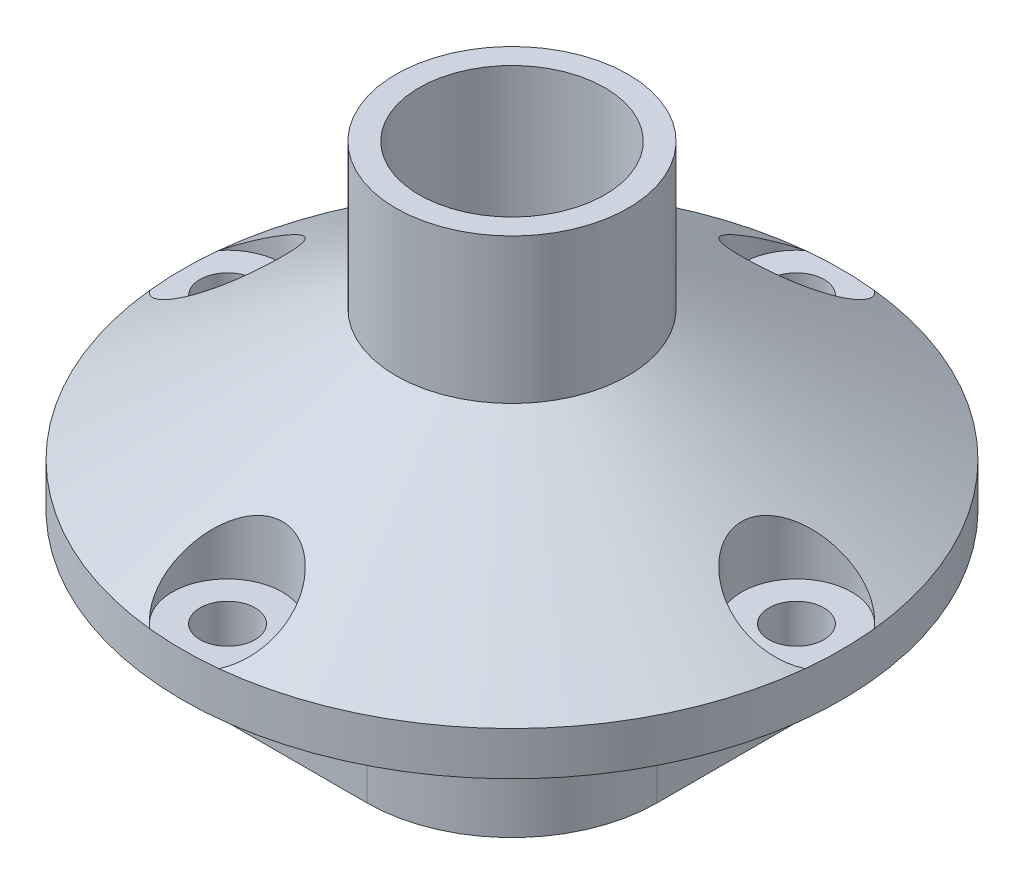
SolidWorks part; units mm, degrees
ref_plane "Front Plane" through (0, 0, 0) normal (0, 0, 1) x (1, 0, 0)
ref_plane "Top Plane" through (0, 0, 0) normal (0, 1, 0) x (1, 0, 0)
ref_plane "Right Plane" through (0, 0, 0) normal (1, 0, 0) x (0, 0, -1)
sketch "Sketch1" plane through (0, 0, 0) normal (0, 0, 1) x (1, 0, 0)
  line L0 (0, 0) -> (0, 14.9728) construction
  line L1 (-5.025, 0) -> (-11.357, 0)
  line L2 (-11.357, 0) -> (-11.357, 4.5)
  line L6 (-4, 9) -> (-4, 14)
  line L7 (-4, 14) -> (-3.2, 14)
  line L8 (-3.2, 14) -> (-3.2, 6)
  line L9 (-3.2, 6) -> (-5.025, 6)
  line L10 (-5.025, 6) -> (-5.025, 0)
  line L22 (-11.357, 4.5) -> (-4, 9)
  dimension "D7" = 4.5
  dimension "D2" = 10.05
  dimension "D3" = 6.4
  dimension "D4" = 8
  dimension "D5" = 5
  dimension "D6" = 6
  dimension "D8" = 22.714
  dimension "1" = 9
revolve "Revolve1" add sketch "Sketch1" angle 360 about L0
sketch "Sketch4" plane through (0, 0, 0) normal (0, 1, 0) x (1, 0, 0)
  line L4 (-3.25, 8.25) -> (0.6616, 8.25)
  line L6 (-8.25, -3.25) -> (-8.25, 0.6616)
  line L8 (8.25, -3.25) -> (8.25, 0.6616)
  line L9 (0.6616, 8.25) -> (3.25, 8.25)
  line L10 (8.25, 0.6616) -> (8.25, 3.25)
  line L11 (-3.25, -8.25) -> (3.25, -8.25)
  line L12 (-8.25, 0.6616) -> (-8.25, 3.25)
  line L13 (0, 11.357) -> (0, 8.25) construction
  arc A40 (-3.25, 8.25) -> (-8.25, 3.25) centre (-3.25, 3.25) ccw
  arc A41 (8.25, 3.25) -> (3.25, 8.25) centre (3.25, 3.25) ccw
  arc A42 (3.25, -8.25) -> (8.25, -3.25) centre (3.25, -3.25) ccw
  arc A43 (-8.25, -3.25) -> (-3.25, -8.25) centre (-3.25, -3.25) ccw
  circle A45 centre (0, 0) radius 11.357
  circle A46 centre (0, 0) radius 9.8035 construction
  circle A47 centre (0, 9.8035) radius 0.95
  circle A48 centre (9.8035, 0) radius 0.95
  circle A49 centre (0, -9.8035) radius 0.95
  circle A50 centre (-9.8035, 0) radius 0.95
  circle A53 centre (0, 0) radius 11.357 construction
  point P19 (0, 0)
  point P28 (0, 0)
  point P34 (0, 0)
  dimension "D1" = 16.5
  dimension "D2" = 5
  dimension "D3" = 4
  dimension "D4" = 1.9
  dimension "D5" = 4
extrude "Cut-Extrude1" cut sketch "Sketch4" along normal blind 3 contours A45 A43 L6 A40 L4 A41 L8 A42 region at (-11.0358, 0, 0)
extrude "Cut-Extrude2" cut sketch "Sketch4<11>" along normal blind 18 contours A47 | A48 | A50 | A49 region at (0, 0, -9.8035) region at (9.8035, 0, 0) region at (-9.8035, 0, 0)
sketch "Sketch4<11>" plane through (0, 0, 0) normal (0, 1, 0) x (1, 0, 0) same geometry as "Sketch4"
ref_plane "Plane1" through (0, 11.375, 0) normal (0, 1, 0) x (1, 0, 0)
sketch "Sketch5" plane through (0, 11.375, 0) normal (0, 1, 0) x (1, 0, 0)
  circle A0 centre (0, 0) radius 9.8125 construction
  circle A1 centre (0, 9.8125) radius 1.9
  circle A2 centre (9.8125, 0) radius 1.9
  circle A3 centre (0, -9.8125) radius 1.9
  circle A4 centre (-9.8125, 0) radius 1.9
  point P14 (0, 0)
  dimension "D1" = 3.8
  dimension "D2" = 4
extrude "Cut-Extrude3" cut sketch "Sketch5" against normal offset from surface (6.875 mm away) 1.5 up to face at (-9.8035, 3, 0.95)
